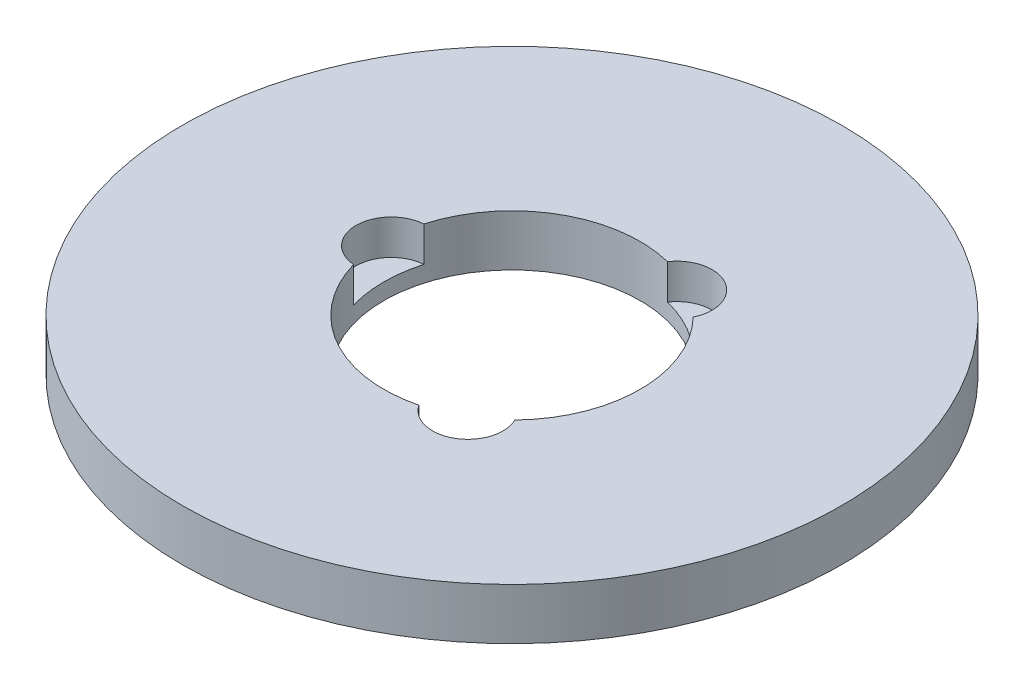
SolidWorks part; units mm, degrees
ref_plane "Front Plane" through (0, 0, 0) normal (0, 0, 1) x (1, 0, 0)
ref_plane "Top Plane" through (0, 0, 0) normal (0, 1, 0) x (1, 0, 0)
ref_plane "Right Plane" through (0, 0, 0) normal (1, 0, 0) x (0, 0, -1)
sketch "Sketch1" plane through (0, 0, 0) normal (0, 1, 0) x (1, 0, 0)
  circle A0 centre (0, 0) radius 90
  dimension "FLANGE_OD" = 180
extrude "Boss-Extrude1" add sketch "Sketch1" along normal blind 14
sketch "Sketch2" plane through (0, 0, 0) normal (0, 1, 0) x (1, 0, 0)
  circle A0 centre (0, 0) radius 35
  dimension "BORE_D" = 70
extrude "Cut-Extrude1" cut sketch "Sketch2" along normal through all
sketch "Sketch3" plane through (0, 14, 0) normal (0, 1, 0) x (1, 0, 0)
  circle A0 centre (0, 0) radius 32.9606 construction
  circle A1 centre (-32.9606, 0) radius 9.6214
  dimension "BOLT_D" = 19.2429
  dimension "BOLT_PCD" = 65.9213
extrude "Cut-Extrude2" cut sketch "Sketch3" against normal blind 9.567
pattern_circular "CirPattern1" count 3 over 360 about axis through (0, 0, 0) along (0, 1, 0) of "Cut-Extrude2"
